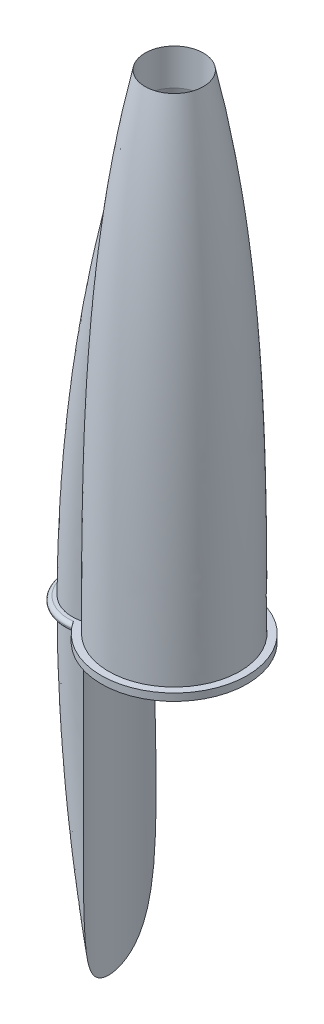
SolidWorks part; units mm, degrees
ref_plane "Alzado" through (0, 0, 0) normal (0, 0, 1) x (1, 0, 0)
ref_plane "Planta" through (0, 0, 0) normal (0, 1, 0) x (1, 0, 0)
ref_plane "Vista lateral" through (0, 0, 0) normal (1, 0, 0) x (0, 0, -1)
sketch "Croquis1" plane through (0, 0, 0) normal (0, 0, 1) x (1, 0, 0)
  line L0 (0, 0) -> (0, 37.6987) construction
  line L1 (4, 0) -> (5, 0)
  line L2 (5, 0) -> (5, 34) construction
  line L3 (5, 34) -> (0, 34) construction
  line L4 (5, 0) -> (5, 0.5)
  line L5 (5, 0.5) -> (4.5, 0.5)
  line L6 (0, 34) -> (2, 34)
  line L7 (4, 0.5) -> (4, 0)
  line L8 (2, 34) -> (2, 31.5013)
  line L9 (4, 0) -> (0, 0)
  line L10 (0, 0) -> (0, 34)
  line L11 (0, 34) -> (-0.0201, 33.9688)
  spline S0 degree 3 poles (2, 34) (4.4043, 23.0634) (4.5, 11.7004) (4.5, 0.5) knots 0 0 0 0 1 1 1 1
  spline S2 degree 3 poles (2, 31.5013) (2.883, 26.8308) (3.9547, 16.5379) (4, 6.1079) (4, 0.5) knots 0.073058 0.073058 0.073058 0.073058 0.5 1 1 1 1
  dimension "D1" = 34
  dimension "D2" = 5
  dimension "D3" = 0.5
  dimension "D4" = 0.5
  dimension "D5" = 2
revolve "Revolución1" add sketch "Croquis1" angle 360 about L0 region at (4.3413, 0.25, 0)
sketch "Croquis2" plane through (0, 0, 0) normal (0, 0, 1) x (1, 0, 0)
  line L0 (-5, 0) -> (-7, 0) construction
  spline S0 degree 2 poles (-7, 0) (-7, 13.6304) (-3.2379, 27) knots 0 0 0 1 1 1
  spline S1 degree 3 poles (-2, 34) (-2.0165, 33.9247) (-2.0495, 33.7741) (-2.0981, 33.5481) (-2.1461, 33.3219) (-2.1935, 33.0956) (-2.2403, 32.8692) (-2.2864, 32.6427) (-2.3319, 32.4161) (-2.3774, 32.1857) (-2.423, 31.9516) (-2.4687, 31.7139) (-2.5137, 31.476) (-2.558, 31.2379) (-2.6016, 30.9998) (-2.6446, 30.7615) (-2.6869, 30.5232) (-2.7286, 30.2847) (-2.7696, 30.0461) (-2.81, 29.8074) (-2.8498, 29.5686) (-2.8882, 29.3342) (-2.9253, 29.1043) (-2.9611, 28.8788) (-2.9963, 28.6532) (-3.031, 28.4276) (-3.0659, 28.1973) (-3.1008, 27.9623) (-3.1359, 27.7227) (-3.1704, 27.483) (-3.2043, 27.2432) (-3.2376, 27.0033) (-3.2697, 26.7678) (-3.3006, 26.5369) (-3.3305, 26.3104) (-3.3598, 26.0839) (-3.3887, 25.8573) (-3.4196, 25.6097) (-3.4525, 25.3413) (-3.4872, 25.0519) (-3.5211, 24.7624) (-3.5543, 24.4728) (-3.5867, 24.1831) (-3.6183, 23.8932) (-3.6492, 23.6034) (-3.6793, 23.3138) (-3.7087, 23.0242) (-3.7374, 22.7346) (-3.7654, 22.4448) (-3.7926, 22.1567) (-3.8189, 21.8702) (-3.8444, 21.5853) (-3.8692, 21.3004) (-3.8936, 21.0134) (-3.9175, 20.7244) (-3.941, 20.4334) (-3.9638, 20.1423) (-3.9859, 19.8511) (-4.0075, 19.5598) (-4.0284, 19.2684) (-4.0488, 18.977) (-4.0685, 18.6855) (-4.0877, 18.3939) (-4.1063, 18.1023) (-4.1243, 17.8106) (-4.1418, 17.5188) (-4.1587, 17.227) (-4.1757, 16.9254) (-4.1925, 16.614) (-4.2093, 16.2928) (-4.2255, 15.9715) (-4.2411, 15.6502) (-4.2568, 15.312) (-4.2726, 14.9569) (-4.2885, 14.5849) (-4.3035, 14.2129) (-4.3179, 13.8408) (-4.3315, 13.4686) (-4.3445, 13.0964) (-4.3571, 12.7118) (-4.3695, 12.3147) (-4.3815, 11.9052) (-4.3927, 11.4956) (-4.4032, 11.086) (-4.413, 10.6764) (-4.4221, 10.2667) (-4.4306, 9.8571) (-4.4384, 9.4475) (-4.4456, 9.0378) (-4.4522, 8.6307) (-4.4583, 8.2259) (-4.4638, 7.8237) (-4.4687, 7.4214) (-4.4737, 6.9792) (-4.4785, 6.497) (-4.483, 5.9748) (-4.4868, 5.4527) (-4.4901, 4.9307) (-4.4927, 4.4088) (-4.4949, 3.8871) (-4.4967, 3.3481) (-4.498, 2.792) (-4.499, 2.2186) (-4.4996, 1.6455) (-4.5, 1.0727) (-4.5, 0.6909) (-4.5, 0.5) knots 0 0 0 0 0.00687 0.013739 0.020607 0.027475 0.034343 0.04121 0.048077 0.054943 0.062136 0.069329 0.076521 0.083714 0.090906 0.098098 0.10529 0.112482 0.119674 0.126866 0.134058 0.141251 0.148032 0.154814 0.161596 0.168378 0.175161 0.182354 0.189549 0.196743 0.203938 0.211133 0.218329 0.225114 0.2319 0.238686 0.245472 0.252259 0.260916 0.269574 0.278234 0.286894 0.295555 0.304216 0.312879 0.321524 0.33017 0.338816 0.347464 0.356113 0.364608 0.373104 0.381602 0.3901 0.398772 0.407446 0.416121 0.424796 0.433473 0.44215 0.450829 0.459508 0.468188 0.47687 0.485552 0.494235 0.502919 0.511603 0.521157 0.530713 0.540268 0.549825 0.559383 0.570442 0.581502 0.592564 0.603626 0.614688 0.625752 0.636816 0.648987 0.661158 0.67333 0.685502 0.697674 0.709845 0.722017 0.734189 0.746359 0.75853 0.770482 0.782433 0.794383 0.806332 0.821848 0.837362 0.852872 0.868379 0.883882 0.899381 0.914876 0.931915 0.948947 0.965972 0.98299 1 1 1 1 construction
  dimension "D1" = 2
  dimension "D2" = 27
sketch "Croquis3" plane through (0, 0, 0) normal (0, 1, 0) x (1, 0, 0)
  line L0 (-5, 0) -> (-7, 0) construction
  circle A0 centre (-4.5, 0) radius 2.5
  dimension "D1" = 5
sweep "Barrer2" add profiles "Croquis3" path "Croquis2"
revolve "Cortar-Revolución4" cut sketch "Croquis1<5>" angle 360 about L10 region at (1.7574, 15.1904, 0)
sketch "Croquis1<5>" plane through (0, 0, 0) normal (0, 0, 1) x (1, 0, 0) same geometry as "Croquis1"
mirror "Simetría1" about plane through (0, 0, 0) normal (0, -1, 0) of "Barrer2"
sketch "Croquis5" plane through (0, 0, 0) normal (0, -1, 0) x (1, 0, 0)
  circle A0 centre (0, 0) radius 4.5
extrude "Cortar-Extruir1" cut sketch "Croquis5" along normal through all
chamfer "Chaflán1" distance 0.5 angle 45 1 edges at (0, 0, -4)
sketch "Croquis6" plane through (0, 0, 0) normal (0, 1, 0) x (1, 0, 0)
  circle A0 centre (0, 0) radius 5
  arc A2 (-4.0278, 2.9626) -> (-4.0278, -2.9626) centre (-4.5, 0) ccw
  dimension "D1" = 6
extrude "Saliente-Extruir1" add sketch "Croquis6" along normal blind 0.5 contours A0 A2 region at (-5.8537, 0, 0)
fillet "Redondeo1" radius 0.25 2 edges at (-7.5, 0, 0) (-7.5, 0.5, 0)
